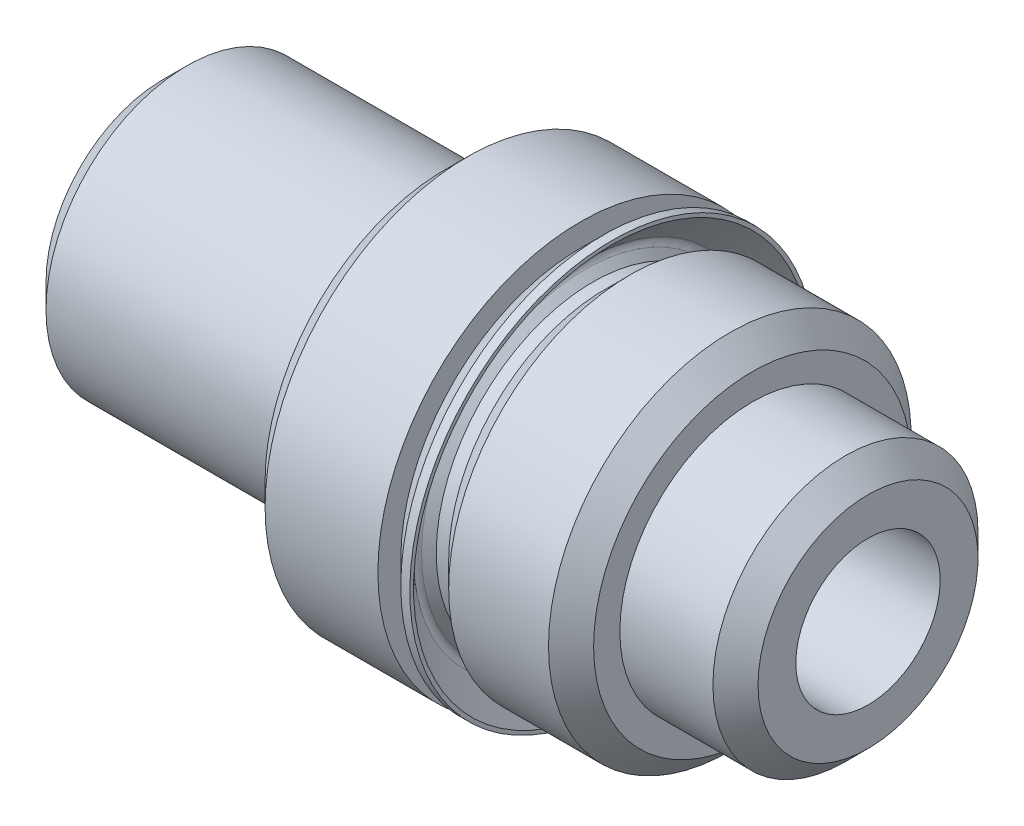
SolidWorks part; units mm, degrees
ref_plane "Front Plane" through (0, 0, 0) normal (0, 0, 1) x (1, 0, 0)
ref_plane "Top Plane" through (0, 0, 0) normal (0, 1, 0) x (1, 0, 0)
ref_plane "Right Plane" through (0, 0, 0) normal (1, 0, 0) x (0, 0, -1)
sketch "Sketch1" plane through (0, 0, 0) normal (0, 0, 1) x (1, 0, 0)
  line L0 (0, 0) -> (0, 2.634)
  line L1 (0, 2.634) -> (0.541, 3.175)
  line L2 (0.541, 3.175) -> (6.35, 3.175)
  line L3 (6.35, 3.175) -> (6.35, 0)
  line L4 (6.35, 0) -> (0, 0)
  line L5 (6.35, 0) -> (0, 0) construction
revolve "Revolve1" add sketch "Sketch1" angle 360 about L5 reverse direction yes
cosmetic thread "Cosmetic Thread1" parameters "D1"=6.35, "D2"=5.268
sketch "Sketch2" plane through (0, 0, 0) normal (0, 0, 1) x (1, 0, 0)
  line L0 (6.35, 0) -> (6.35, 4.0513)
  line L1 (6.35, 4.0513) -> (6.858, 4.5593)
  line L2 (6.858, 4.5593) -> (9.398, 4.5593)
  line L3 (9.398, 4.5593) -> (9.398, 3.5242)
  line L4 (9.398, 3.5242) -> (9.9568, 3.5242)
  line L5 (9.9568, 3.5242) -> (10.5156, 4.0831)
  line L6 (10.5156, 4.0831) -> (12.7635, 4.0831)
  line L7 (12.7635, 4.0831) -> (13.2715, 3.5751)
  line L8 (13.2715, 3.5751) -> (13.2715, 0)
  line L9 (13.2715, 0) -> (6.35, 0)
  line L10 (13.2715, 0) -> (6.35, 0) construction
revolve "Revolve2" add sketch "Sketch2" angle 360 about L10 reverse direction yes
sketch "Sketch3" plane through (0, 0, 0) normal (0, 0, 1) x (1, 0, 0)
  line L0 (13.2715, 0) -> (13.2715, 2.9845)
  line L1 (13.2715, 2.9845) -> (15.367, 2.9845)
  line L2 (15.367, 2.9845) -> (15.875, 2.4765)
  line L3 (15.875, 2.4765) -> (15.875, 0)
  line L4 (15.875, 0) -> (13.2715, 0)
  line L5 (15.875, 0) -> (13.2715, 0) construction
revolve "Revolve3" add sketch "Sketch3" angle 360 about L5 reverse direction yes
hole_wizard "Hole1" positions "Sketch5" profile "Sketch4" legacy
sketch "Sketch5" plane through (0, 0, 0) normal (-1, 0, 0) x (0, 0, 1)
  point P0 (0, 0)
sketch "Sketch4" plane through (0, 0, 0) normal (0, 1, 0) x (0, 0, 1)
  line L0 (0, 0) -> (0, 15.875)
  line L1 (0, 15.875) -> (1.6256, 15.875)
  line L2 (1.6256, 15.875) -> (1.6256, 0.381)
  line L3 (1.6256, 0.381) -> (2.0066, 0)
  line L4 (2.0066, 0) -> (0, 0)
  line L5 (0, -6.4453) -> (0, 115.525) construction
  line L6 (-1.6256, 0.381) -> (-2.0066, 0) construction
  dimension "Diameter" = 3.2512
  dimension "Depth" = 15.875
  dimension "C-Sink Angle" = 90
  dimension "C-Sink Diameter" = 4.0132
ref_plane "Plane1" through (15.0876, 0, 0) normal (1, 0, 0) x (0, 0, -1)
ref_plane "Plane2" through (15.0876, 0, 0) normal (1, 0, 0) x (0, 0, -1)
ref_plane "Plane3" through (0, 0, 0) normal (0, -0.7071, 0.7071) x (1, 0, 0)
ref_plane "Plane4" through (0, 0, 0) normal (1, 0, 0) x (0, 0, -1)
ref_plane "Plane5" through (9.398, 0, 0) normal (1, 0, 0) x (0, 0, -1)
ref_plane "Plane6" through (6.35, 0, 0) normal (1, 0, 0) x (0, 0, -1)
ref_plane "Plane7" through (9.398, 0, 0) normal (1, 0, 0) x (0, 0, -1)
sketch "Sketch6" plane through (0, 0, 0) normal (0, 0, 1) x (1, 0, 0)
  line L0 (9.398, 3.2703) -> (9.9568, 3.2703)
  line L1 (9.9568, 3.2703) -> (9.9568, 3.5242)
  line L2 (9.9568, 3.5242) -> (9.6774, 3.5242)
  line L3 (9.6774, 3.5242) -> (9.5118, 3.6899)
  line L4 (9.5118, 3.8695) -> (10.1174, 4.4751)
  line L5 (10.1174, 4.4751) -> (10.1174, 4.5593)
  line L6 (10.1174, 4.5593) -> (9.9142, 4.5593)
  line L7 (9.9142, 4.5593) -> (9.398, 4.0431)
  line L8 (9.398, 4.0431) -> (9.398, 3.2703)
  line L9 (9.9568, 0) -> (9.398, 0) construction
  arc A0 (9.5118, 3.6899) -> (9.5118, 3.8695) centre (9.6016, 3.7797) cw
revolve "Revolve4" add sketch "Sketch6" angle 360 about L9 reverse direction yes
ref_plane "Plane8" through (9.9568, 0, 0) normal (1, 0, 0) x (0, 0, -1)
ref_plane "Plane9" through (6.35, 0, 0) normal (1, 0, 0) x (0, 0, -1)
ref_plane "Plane10" through (6.35, 0, 0) normal (1, 0, 0) x (0, 0, -1)
ref_plane "Plane11" through (0, 6.35, 0) normal (0, 1, 0) x (1, 0, 0)
ref_plane "Plane12" through (0, -6.35, 0) normal (0, 1, 0) x (1, 0, 0)
ref_plane "Plane13" through (6.35, 0, 0) normal (1, 0, 0) x (0, 0, -1)
ref_plane "Plane14" through (0, 0, 0) normal (0, 1, 0) x (1, 0, 0)
ref_plane "Plane15" through (0, 0, 0) normal (0, 1, 0) x (1, 0, 0)
ref_plane "Plane16" through (0, 0, 0) normal (0, 1, 0) x (1, 0, 0)
ref_plane "Plane17" through (0, 0, 0) normal (1, 0, 0) x (0, 0, -1)
ref_plane "rod_guide XY" through (0, 0, 0) normal (1, 0, 0) x (0, 0, -1)
ref_plane "rod_guide XZ" through (0, 0, 0) normal (0, -1, 0) x (-1, 0, 0)
ref_plane "rod_guide YZ" through (0, 0, 0) normal (0, 0, -1) x (-1, 0, 0)
ref_axis "rod_guide X" through (0, 0, 80.9) along (0, 0, -1)
ref_axis "rod_guide Y" through (0, -50, 0) along (0, 1, 0)
ref_axis "rod_guide Z" through (80.9, 0, 0) along (-1, 0, 0)
sketch3d "rod_guide"
  point P0 (0, 0, 0)
ref_plane "t1 XY" through (6.35, 0, 0) normal (1, 0, 0) x (0, 0, -1)
ref_plane "t1 XZ" through (0, 0, 0) normal (0, -1, 0) x (-1, 0, 0)
ref_plane "t1 YZ" through (0, 0, 0) normal (0, 0, -1) x (-1, 0, 0)
ref_axis "t1 X" through (6.35, 0, 80.9) along (0, 0, -1)
ref_axis "t1 Y" through (6.35, -50, 0) along (0, 1, 0)
ref_axis "t1 Z" through (80.9, 0, 0) along (-1, 0, 0)
sketch3d "t1"
  point P0 (6.35, 0, 0)
ref_plane "t111 XY" through (6.35, 0, 0) normal (1, 0, 0) x (0, 0, -1)
ref_plane "t111 XZ" through (0, 0, 0) normal (0, -1, 0) x (-1, 0, 0)
ref_plane "t111 YZ" through (0, 0, 0) normal (0, 0, -1) x (-1, 0, 0)
ref_axis "t111 X" through (6.35, 0, 80.9) along (0, 0, -1)
ref_axis "t111 Y" through (6.35, -50, 0) along (0, 1, 0)
ref_axis "t111 Z" through (80.9, 0, 0) along (-1, 0, 0)
sketch3d "t111"
  point P0 (6.35, 0, 0)
ref_plane "to_foot_bracket XY" through (6.35, 0, 0) normal (1, 0, 0) x (0, 0, -1)
ref_plane "to_foot_bracket XZ" through (0, 0, 0) normal (0, -1, 0) x (-1, 0, 0)
ref_plane "to_foot_bracket YZ" through (0, 0, 0) normal (0, 0, -1) x (-1, 0, 0)
ref_axis "to_foot_bracket X" through (6.35, 0, 80.9) along (0, 0, -1)
ref_axis "to_foot_bracket Y" through (6.35, -50, 0) along (0, 1, 0)
ref_axis "to_foot_bracket Z" through (80.9, 0, 0) along (-1, 0, 0)
sketch3d "to_foot_bracket"
  point P0 (6.35, 0, 0)
ref_plane "to_nut XY" through (6.35, 0, 0) normal (1, 0, 0) x (0, 0, -1)
ref_plane "to_nut XZ" through (0, 0, 0) normal (0, -1, 0) x (-1, 0, 0)
ref_plane "to_nut YZ" through (0, 0, 0) normal (0, 0, -1) x (-1, 0, 0)
ref_axis "to_nut X" through (6.35, 0, 80.9) along (0, 0, -1)
ref_axis "to_nut Y" through (6.35, -50, 0) along (0, 1, 0)
ref_axis "to_nut Z" through (80.9, 0, 0) along (-1, 0, 0)
sketch3d "to_nut"
  point P0 (6.35, 0, 0)
ref_plane "to_rod XY" through (0, 0, 0) normal (1, 0, 0) x (0, 0, -1)
ref_plane "to_rod XZ" through (0, 0, 0) normal (0, -1, 0) x (-1, 0, 0)
ref_plane "to_rod YZ" through (0, 0, 0) normal (0, 0, -1) x (-1, 0, 0)
ref_axis "to_rod X" through (0, 0, 80.9) along (0, 0, -1)
ref_axis "to_rod Y" through (0, -50, 0) along (0, 1, 0)
ref_axis "to_rod Z" through (80.9, 0, 0) along (-1, 0, 0)
sketch3d "to_rod"
  point P0 (0, 0, 0)
ref_plane "to_screw XY" through (0, 0, 0) normal (0, 1, 0) x (1, 0, 0)
ref_plane "to_screw XZ" through (0, 0, 0) normal (0, 0, 1) x (1, 0, 0)
ref_plane "to_screw YZ" through (6.35, 0, 0) normal (1, 0, 0) x (0, 0, -1)
ref_axis "to_screw X" through (-80.9, 0, 0) along (1, 0, 0)
ref_axis "to_screw Y" through (6.35, 0, 50) along (0, 0, -1)
ref_axis "to_screw Z" through (6.35, 50, 0) along (0, -1, 0)
sketch3d "to_screw"
  point P0 (6.35, 0, 0)
ref_plane "to_trunnion_brackets XY" through (0, 0, 0) normal (0, 1, 0) x (1, 0, 0)
ref_plane "to_trunnion_brackets XZ" through (0, 0, 0) normal (0, 0, 1) x (1, 0, 0)
ref_plane "to_trunnion_brackets YZ" through (0, 0, 0) normal (1, 0, 0) x (0, 0, -1)
ref_axis "to_trunnion_brackets X" through (-80.9, 0, 0) along (1, 0, 0)
ref_axis "to_trunnion_brackets Y" through (0, 0, 50) along (0, 0, -1)
ref_axis "to_trunnion_brackets Z" through (0, 50, 0) along (0, -1, 0)
sketch3d "to_trunnion_brackets"
  point P0 (0, 0, 0)
ref_plane "to_trunnion_brackets1 XY" through (0, 6.35, 0) normal (0, 1, 0) x (1, 0, 0)
ref_plane "to_trunnion_brackets1 XZ" through (0, 0, 0) normal (0, 0, 1) x (1, 0, 0)
ref_plane "to_trunnion_brackets1 YZ" through (0, 0, 0) normal (1, 0, 0) x (0, 0, -1)
ref_axis "to_trunnion_brackets1 X" through (-80.9, 6.35, 0) along (1, 0, 0)
ref_axis "to_trunnion_brackets1 Y" through (0, 6.35, 50) along (0, 0, -1)
ref_axis "to_trunnion_brackets1 Z" through (0, 50, 0) along (0, -1, 0)
sketch3d "to_trunnion_brackets1"
  point P0 (0, 6.35, 0)
ref_plane "to_trunnion_brackets2 XY" through (0, -6.35, 0) normal (0, 1, 0) x (1, 0, 0)
ref_plane "to_trunnion_brackets2 XZ" through (0, 0, 0) normal (0, 0, 1) x (1, 0, 0)
ref_plane "to_trunnion_brackets2 YZ" through (0, 0, 0) normal (1, 0, 0) x (0, 0, -1)
ref_axis "to_trunnion_brackets2 X" through (-80.9, -6.35, 0) along (1, 0, 0)
ref_axis "to_trunnion_brackets2 Y" through (0, -6.35, 50) along (0, 0, -1)
ref_axis "to_trunnion_brackets2 Z" through (0, 50, 0) along (0, -1, 0)
sketch3d "to_trunnion_brackets2"
  point P0 (0, -6.35, 0)
ref_plane "to_tube XY" through (9.9568, 0, 0) normal (1, 0, 0) x (0, 0, -1)
ref_plane "to_tube XZ" through (0, 0, 0) normal (0, -1, 0) x (-1, 0, 0)
ref_plane "to_tube YZ" through (0, 0, 0) normal (0, 0, -1) x (-1, 0, 0)
ref_axis "to_tube X" through (9.9568, 0, 80.9) along (0, 0, -1)
ref_axis "to_tube Y" through (9.9568, -50, 0) along (0, 1, 0)
ref_axis "to_tube Z" through (80.9, 0, 0) along (-1, 0, 0)
sketch3d "to_tube"
  point P0 (9.9568, 0, 0)
